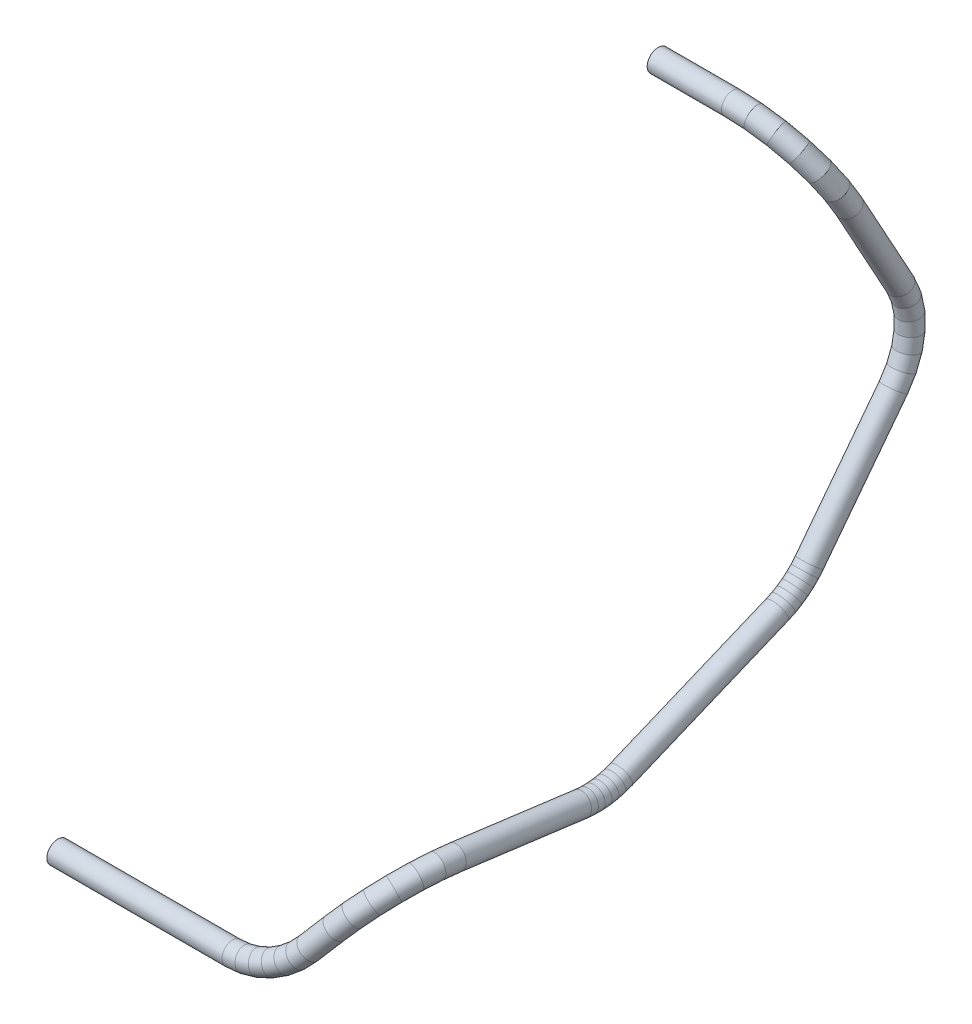
SolidWorks part; units mm, degrees
ref_plane "Front Plane" through (0, 0, 0) normal (0, 0, 1) x (1, 0, 0)
ref_plane "Top Plane" through (0, 0, 0) normal (0, 1, 0) x (1, 0, 0)
ref_plane "Right Plane" through (0, 0, 0) normal (1, 0, 0) x (0, 0, -1)
sketch3d "Path"
  line L0 (-571, -108.3711, 44.8888) -> (-531.0671, -108.3711, 44.8888)
  line L1 (-531.0671, -108.3711, 44.8888) -> (-528.2786, -108.1703, 44.8056)
  line L2 (-528.2786, -108.1703, 44.8056) -> (-525.5575, -107.5729, 44.5581)
  line L3 (-525.5575, -107.5729, 44.5581) -> (-522.9693, -106.5932, 44.1524)
  line L4 (-522.9693, -106.5932, 44.1524) -> (-520.5767, -105.2549, 43.598)
  line L5 (-520.5767, -105.2549, 43.598) -> (-518.4374, -103.5904, 42.9086)
  line L6 (-518.4374, -103.5904, 42.9086) -> (-516.603, -101.6398, 42.1006)
  line L7 (-516.603, -101.6398, 42.1006) -> (-512.6755, -96.7412, 40.0715)
  line L8 (-512.6755, -96.7412, 40.0715) -> (-510.3239, -93.8697, 38.389)
  line L9 (-510.3239, -93.8697, 38.389) -> (-508.2095, -91.4141, 35.918)
  line L10 (-508.2095, -91.4141, 35.918) -> (-506.4408, -89.5003, 32.785)
  line L11 (-506.4408, -89.5003, 32.785) -> (-505.1085, -88.2264, 29.1506)
  line L12 (-505.1085, -88.2264, 29.1506) -> (-504.2807, -87.6577, 25.2012)
  line L13 (-504.2807, -87.6577, 25.2012) -> (-504, -87.8232, 21.1391)
  line L14 (-504, -87.8232, 21.1391) -> (-504, -91.5748, -7.3571)
  line L15 (-504, -91.5748, -7.3571) -> (-504, -91.7117, -8.9214)
  line L16 (-504, -91.7117, -8.9214) -> (-504, -91.7117, -10.4917)
  line L17 (-504, -91.7117, -10.4917) -> (-504, -91.5748, -12.0561)
  line L18 (-504, -91.5748, -12.0561) -> (-504, -91.3022, -13.6025)
  line L19 (-504, -91.3022, -13.6025) -> (-504, -90.8957, -15.1193)
  line L20 (-504, -90.8957, -15.1193) -> (-504, -90.3587, -16.5949)
  line L21 (-504, -90.3587, -16.5949) -> (-504, -75.6276, -52.1589)
  line L22 (-504, -75.6276, -52.1589) -> (-504, -74.9639, -53.582)
  line L23 (-504, -74.9639, -53.582) -> (-504, -74.1788, -54.942)
  line L24 (-504, -74.1788, -54.942) -> (-504, -73.2781, -56.2283)
  line L25 (-504, -73.2781, -56.2283) -> (-504, -72.2687, -57.4312)
  line L26 (-504, -72.2687, -57.4312) -> (-504, -71.1584, -58.5416)
  line L27 (-504, -71.1584, -58.5416) -> (-504, -69.9554, -59.5509)
  line L28 (-504, -69.9554, -59.5509) -> (-504, -44.9204, -78.761)
  line L29 (-504, -44.9204, -78.761) -> (-504, -41.9792, -80.597)
  line L30 (-504, -41.9792, -80.597) -> (-504, -38.7405, -81.8349)
  line L31 (-504, -38.7405, -81.8349) -> (-504, -35.3246, -82.429)
  line L32 (-504, -35.3246, -82.429) -> (-504, -31.8581, -82.3572)
  line L33 (-504, -31.8581, -82.3572) -> (-504, -28.4698, -81.622)
  line L34 (-504, -28.4698, -81.622) -> (-504, -25.2852, -80.2509)
  line L35 (-504, -25.2852, -80.2509) -> (-504, -4.0703, -68.5775)
  line L36 (-504, -4.0703, -68.5775) -> (-504.6133, 0.0114, -66.3316)
  line L37 (-504.6133, 0.0114, -66.3316) -> (-506.4115, 3.8149, -64.2387)
  line L38 (-506.4115, 3.8149, -64.2387) -> (-509.2721, 7.081, -62.4416)
  line L39 (-509.2721, 7.081, -62.4416) -> (-513, 9.5872, -61.0626)
  line L40 (-513, 9.5872, -61.0626) -> (-517.3413, 11.1626, -60.1957)
  line L41 (-517.3413, 11.1626, -60.1957) -> (-522, 11.7, -59.9)
  line L42 (-522, 11.7, -59.9) -> (-538.85, 11.7, -59.9)
ref_plane "Start Plane" through (-571, 0, 0) normal (1, 0, 0) x (0, 0, -1)
sketch "Profile" plane through (-571, 0, 0) normal (1, 0, 0) x (0, 0, -1)
  circle A0 centre (-44.8888, -108.3711) radius 2.5
  circle A1 centre (-44.8888, -108.3711) radius 1
sweep "Tube" add profiles "Profile" path "Path"
ref_axis "Engine Axis" through (-498.025, 0, 0) along (-1, 0, 0)
